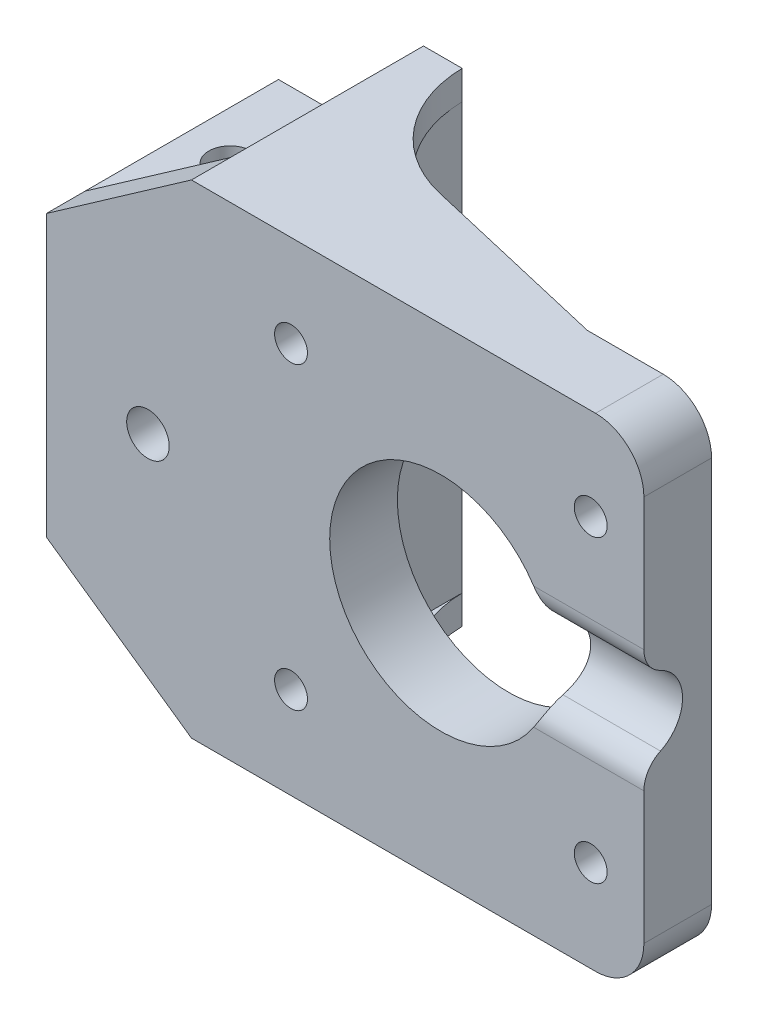
SolidWorks part; units mm, degrees
note: The reader was unsure of these and kept them because the rebuilt part matched: shared geometry of "草图3<3>", "草图6<2>".
ref_plane "前视基准面" through (0, 0, 0) normal (0, 0, 1) x (1, 0, 0)
ref_plane "上视基准面" through (0, 0, 0) normal (0, 1, 0) x (1, 0, 0)
ref_plane "右视基准面" through (0, 0, 0) normal (1, 0, 0) x (0, 0, -1)
sketch "草图3" plane through (0, 0, 0) normal (0, 0, 1) x (1, 0, 0)
  line L0 (-756.9626, 0) -> (37091.1692, 0) construction
  line L1 (-756.9626, 10) -> (37091.1692, 10) construction
  line L2 (-755.7686, -10) -> (37092.3632, -10) construction
  line L3 (-40.8, 10.5) -> (-40.8, 14.5)
  line L4 (-21, -21) -> (21, -21) construction
  line L5 (-21, -21) -> (-21, 21) construction
  line L6 (-21, 21) -> (21, 21) construction
  line L7 (21, -21) -> (21, 21) construction
  line L8 (-21, -21) -> (21, 21) construction
  line L9 (-21, 21) -> (21, -21) construction
  line L10 (-40.8, 10.5) -> (-40.8, -10.5)
  line L11 (-21, 21) -> (21, 21)
  line L12 (21, 21) -> (21, -21)
  line L13 (21, -21) -> (-21, -21)
  line L14 (-40.8, 10.5) -> (-25.8, 10.5)
  line L15 (-21.8, 20.7374) -> (-21.8, -20.7374)
  line L16 (-40.8, 14.5) -> (-25.8, 14.5)
  line L17 (-25.8, 21) -> (-25.8, 25)
  line L18 (-25.8, 19.4242) -> (-25.8, 14.5)
  line L19 (-25.8, 25) -> (21, 25)
  line L20 (-40.8, -14.5) -> (-25.8, -14.5)
  line L21 (-40.8, -10.5) -> (-25.8, -10.5)
  line L22 (-40.8, -10.5) -> (-40.8, -14.5)
  line L23 (-25.8, 10.5) -> (-25.8, -10.5)
  line L24 (-25.8, -14.5) -> (-25.8, -19.4242)
  line L25 (-21, -21) -> (-25.8, -21)
  line L26 (-25.8, -21) -> (-25.8, -19.4242)
  line L27 (-21, 21) -> (-25.8, 21)
  line L28 (-25.8, 21) -> (-25.8, 19.4242)
  line L29 (-21.8, -20.7374) -> (-21.8, -21)
  line L30 (-21.8, 20.7374) -> (-21.8, 21)
  line L31 (-40.8, -14.5) -> (-25.8, -25)
  line L32 (-40.8, 14.5) -> (-25.8, 25)
  line L33 (21, 25) -> (21, 21)
  line L34 (-25.8, -21) -> (-25.8, -25)
  line L35 (-25.8, -25) -> (21, -25)
  line L36 (21, -25) -> (21, -21)
  line L37 (-21.8, 21) -> (-21.8, 25)
  line L38 (-21.8, -21) -> (-21.8, -25)
  circle A0 centre (0, 0) radius 11.5
  circle A1 centre (-15.5, 15.5) radius 1.7
  circle A2 centre (15.5, 15.5) radius 1.7
  circle A3 centre (15.5, -15.5) radius 1.7
  circle A4 centre (-15.5, -15.5) radius 1.7
  circle A5 centre (-30.3, 0) radius 2.2
  point P6 (0, 0)
  point P25 (0, 0)
  point P32 (-40.8, 0)
  dimension "D5" = 23
  dimension "D6" = 3.4
  dimension "D14" = 4.4
  dimension "D1" = 10
  dimension "D2" = 10
  dimension "D3" = 42
  dimension "D4" = 42
  dimension "D8" = 31
  dimension "D9" = 21
  dimension "D10" = 4
  dimension "D11" = 15
  dimension "D12" = 0.8
  dimension "D13" = 4
  dimension "D15" = 4.5
  dimension "D16" = 4
  dimension "D17" = 4
  dimension "D7" = 4
extrude "凸台-拉伸1" add sketch "草图3" along normal blind 4
extrude "凸台-拉伸2" add sketch "草图3<3>" against normal blind 20 contours L15 L30 L27 L28 L18 L16 L3 L14 L23 L21 L22 L20 L24 L26 L25 L29 | L27 L37 L19 L17 | L38 L25 L34 L35
sketch "草图3<3>" plane through (0, 0, 0) normal (0, 0, 1) x (1, 0, 0) same geometry as "草图3"
sketch "草图4" plane through (0, -14.5, 0) normal (0, -1, 0) x (1, 0, 0)
  line L0 (-25.8, -20) -> (-25.8, 0) construction
  circle A0 centre (-35.8, -10) radius 2.2
  dimension "D1" = 4.4
  dimension "D2" = 10
  dimension "D3" = 10
extrude "切除-拉伸1" cut sketch "草图4" against normal through all
sketch "草图6" plane through (0, -25, 0) normal (0, -1, 0) x (1, 0, 0)
  line L0 (21, 0) -> (-21.8, -10)
  line L1 (-21.8, -20) -> (-21.8, 0) construction
  line L2 (-21.8, -10) -> (-21.8, 0)
  line L3 (-21.8, 0) -> (21, 0)
extrude "凸台-拉伸7" add sketch "草图6" against normal blind 3
extrude "凸台-拉伸8" add sketch "草图6<2>" along normal blind 3 from vertex
sketch "草图6<2>" plane through (0, -25, 0) normal (0, -1, 0) x (1, 0, 0) same geometry as "草图6"
fillet "圆角2" radius 13 2 edges at (-21.8, 23.5, -10) (-21.8, -23.5, -10)
sketch "草图7" plane through (0, 0, 0) normal (0, 0, -1) x (-1, 0, 0)
  line L4 (21.8, 22) -> (-21, 22)
  line L5 (-21, 22) -> (-21, -22)
  line L6 (-21, -22) -> (21.8, -22)
  line L7 (21.8, -22) -> (21.8, 22)
  line L8 (21.8, 22) -> (-21, 22)
  line L9 (-21, 22) -> (-21, -22)
  line L10 (-21, -22) -> (21.8, -22)
  line L11 (21.8, -22) -> (21.8, 22)
  circle A0 centre (0, 0) radius 11.5 construction
  circle A1 centre (15.5, 15.5) radius 1.7 construction
  circle A6 centre (-15.5, 15.5) radius 1.7 construction
  circle A7 centre (-15.5, -15.5) radius 1.7 construction
  circle A8 centre (15.5, -15.5) radius 1.7 construction
  circle A9 centre (0, 0) radius 11.5
  circle A10 centre (15.5, 15.5) radius 1.7
  circle A11 centre (-15.5, 15.5) radius 1.7
  circle A12 centre (-15.5, -15.5) radius 1.7
  circle A13 centre (15.5, -15.5) radius 1.7
  dimension "D1" = 0
extrude "凸台-拉伸11" add sketch "草图7" along normal blind 3
sketch "草图8" plane through (0, -22, 0) normal (0, -1, 0) x (1, 0, 0)
  line L3 (21, 0) -> (8.16, -3)
  line L4 (8.16, -3) -> (21, -3)
  line L5 (21, -3) -> (21, 0)
  line L6 (21, 0) -> (8.16, -3)
  line L7 (8.16, -3) -> (21, -3)
  line L8 (21, -3) -> (21, 0)
  dimension "D1" = 0
extrude "凸台-拉伸12" add sketch "草图8" along normal blind 3
sketch "草图9" plane through (0, 22, 0) normal (0, 1, 0) x (1, 0, 0)
  line L3 (21, 3) -> (8.16, 3)
  line L4 (8.16, 3) -> (21, 0)
  line L5 (21, 0) -> (21, 3)
  line L6 (21, 3) -> (8.16, 3)
  line L7 (8.16, 3) -> (21, 0)
  line L8 (21, 0) -> (21, 3)
  dimension "D1" = 0
extrude "凸台-拉伸13" add sketch "草图9" along normal blind 3
fillet "圆角6" radius 5 4 edges at (-25.8, -14.5, -10) (-25.8, 14.5, -10) (21, 25, 0.5) (21, -25, 0.5)
sketch "草图10" plane through (21, 0, 0) normal (1, 0, 0) x (0, 0, -1)
  line L0 (-4, 20) -> (-4, -20) construction
  line L4 (-4, -4) -> (-4, 4)
  arc A0 (-4, -4) -> (-4, 4) centre (-4, 0) ccw
  dimension "D1" = 4
extrude "切除-拉伸2" cut sketch "草图10" against normal up to next
fillet "圆角7" radius 3 2 edges at (15.891, -4, 4) (15.891, 4, 4)
